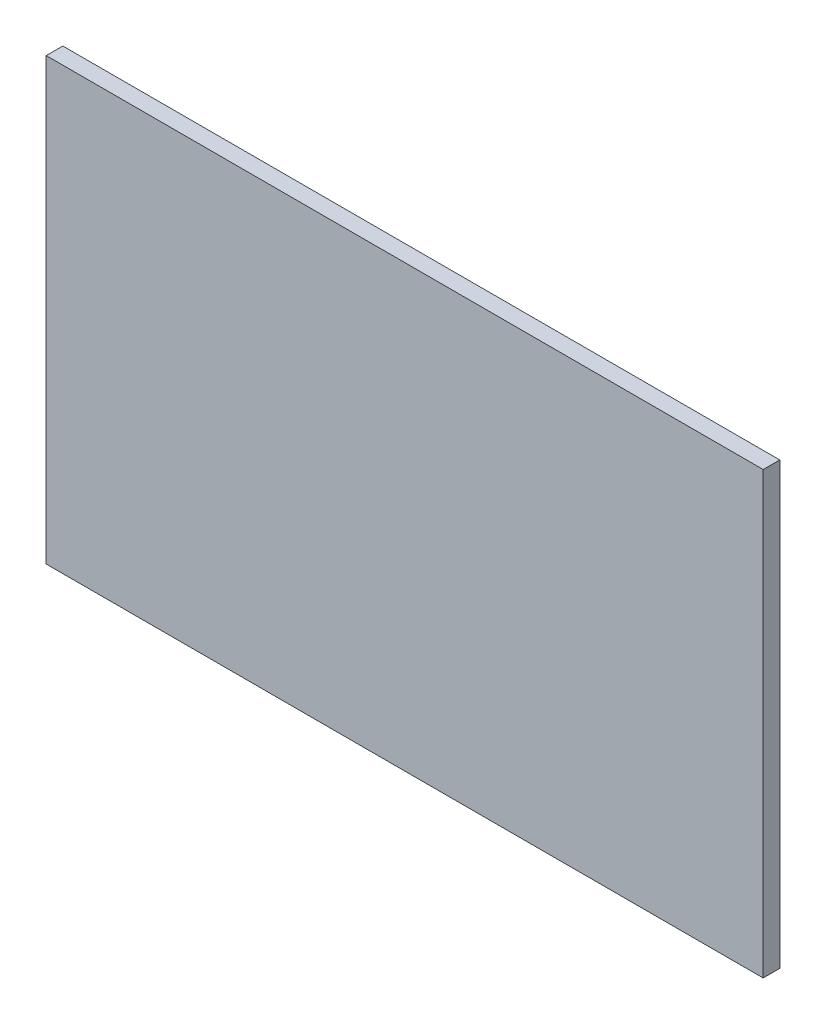
SolidWorks part; units mm, degrees
ref_plane "Přední rovina" through (0, 0, 0) normal (0, 0, 1) x (1, 0, 0)
ref_plane "Horní rovina" through (0, 0, 0) normal (0, 1, 0) x (1, 0, 0)
ref_plane "Pravá rovina" through (0, 0, 0) normal (1, 0, 0) x (0, 0, -1)
sketch "Skica1" plane through (0, 0, 0) normal (0, 0, 1) x (1, 0, 0)
  line L1 (0, 0) -> (129.6, 0)
  line L2 (0, 0) -> (0, 79.6)
  line L3 (0, 79.6) -> (129.6, 79.6)
  line L4 (129.6, 0) -> (129.6, 79.6)
  dimension "D1" = 129.6
  dimension "D2" = 79.6
extrude "Přidat vysunutím1" add sketch "Skica1" along normal blind 3
